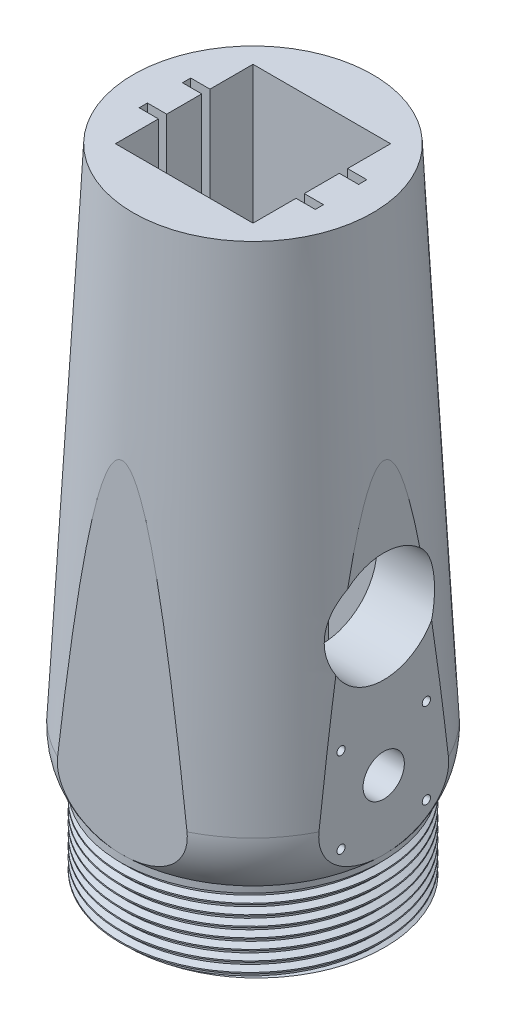
SolidWorks part; units mm, degrees
ref_plane "Front Plane" through (0, 0, 0) normal (0, 0, 1) x (1, 0, 0)
ref_plane "Top Plane" through (0, 0, 0) normal (0, 1, 0) x (1, 0, 0)
ref_plane "Right Plane" through (0, 0, 0) normal (1, 0, 0) x (0, 0, -1)
sketch "Sketch2" plane through (0, 0, 0) normal (0, 1, 0) x (1, 0, 0)
  circle A0 centre (0, 0) radius 47.5
  dimension "D1" = 95
extrude "Boss-Extrude1" add sketch "Sketch2" along normal blind 30
thread "Thread2" pitch 3.6286 method cut profile "Thread Profile2" start angle 0, offset 0, length 30, pitch 3.6286, diameter 95
ref_plane "Plane2" through (-47.5, 30, 0) normal (0, 0, 1) x (-1, 0, 0)
sketch "Thread Profile2" plane through (-47.5, 30, 0) normal (0, 0, 1) x (-1, 0, 0)
  line L0 (0, 0) -> (0, 3.6286) construction
  line L11 (0, 0) -> (0, 3.175)
  line L12 (0, 3.175) -> (-1.964, 2.0411)
  line L13 (-1.964, 2.0411) -> (-1.964, 1.1339)
  line L15 (-1.964, 1.1339) -> (0, 0)
  line L17 (-1.964, 1.5875) -> (0, 1.5875) construction
  point P2 (0, 0)
  dimension "Pitch" = 3.6286
  dimension "Profile_Angle" = 60
  dimension "Profile_Land" = 0.9071
  dimension "Profile_Height" = 1.964
sketch "Sketch12" plane through (0, 30, 0) normal (0, 1, 0) x (1, 0, 0)
  circle A0 centre (0, 0) radius 54
  dimension "D1" = 108
extrude "Boss-Extrude2" add sketch "Sketch12" along normal blind 200 draft 3
sketch "Sketch13" plane through (0, 230, 0) normal (0, 1, 0) x (1, 0, 0)
  line L1 (-25, 25) -> (25, 25)
  line L2 (-25, 25) -> (-25, -25)
  line L3 (-25, -25) -> (25, -25)
  line L4 (25, 25) -> (25, -25)
  line L5 (-25, 25) -> (25, -25) construction
  line L6 (-25, -25) -> (25, 25) construction
  point P0 (0, 0)
  dimension "D1" = 50
  dimension "D2" = 50
extrude "Cut-Extrude2" cut sketch "Sketch13" against normal up to surface (200 mm away) up to face at (0, 30, 54)
sketch "Sketch14" plane through (0, 230, 0) normal (0, 1, 0) x (1, 0, 0)
  line L5 (-47.5, 47.5) -> (47.5, 47.5)
  line L6 (-47.5, 47.5) -> (-47.5, -47.5)
  line L7 (-47.5, -47.5) -> (47.5, -47.5)
  line L8 (47.5, 47.5) -> (47.5, -47.5)
  line L9 (-47.5, 47.5) -> (47.5, -47.5) construction
  line L10 (-47.5, -47.5) -> (47.5, 47.5) construction
  circle A3 centre (0, 0) radius 67.1751
  point P0 (0, 0)
  point P1 (0, 0)
  dimension "D1" = 95
extrude "Cut-Extrude3" cut sketch "Sketch14" against normal up to surface (200 mm away) contours L6 A3 | L5 A3 | L8 A3 | L7 A3 region at (0, 230, -55.478) region at (-55.478, 230, 0) region at (55.478, 230, 0) region at (0, 230, 55.478) up to face at (0, 30, 54)
fillet "Fillet2" radius 30 4 edges at (-38.1838, 30, 38.1838) (-38.1838, 30, -38.1838) (38.1838, 30, 38.1838) (38.1838, 30, -38.1838)
sketch "Sketch15" plane through (-25, 0, 0) normal (1, 0, 0) x (0, 0, -1)
  line L1 (-21.15, 76.15) -> (21.15, 76.15)
  line L2 (-21.15, 76.15) -> (-21.15, 33.85)
  line L3 (-21.15, 33.85) -> (21.15, 33.85)
  line L4 (21.15, 76.15) -> (21.15, 33.85)
  line L5 (-21.15, 76.15) -> (21.15, 33.85) construction
  line L6 (-21.15, 33.85) -> (21.15, 76.15) construction
  point P0 (0, 55)
  dimension "D1" = 42.3
  dimension "D2" = 55
extrude "Cut-Extrude4" cut sketch "Sketch15" against normal up to next
sketch "Sketch16" plane through (0, 0, 25) normal (0, 0, -1) x (-1, 0, 0)
  line L1 (-2.5, 76) -> (2.5, 76)
  line L2 (-2.5, 76) -> (-2.5, 34)
  line L3 (-2.5, 34) -> (2.5, 34)
  line L4 (2.5, 76) -> (2.5, 34)
  line L5 (-2.5, 76) -> (2.5, 34) construction
  line L6 (-2.5, 34) -> (2.5, 76) construction
  point P0 (0, 55)
  dimension "D1" = 42
  dimension "D2" = 55
  dimension "D3" = 5
extrude "Boss-Extrude3" add sketch "Sketch16" along normal up to next
sketch "Sketch17" plane through (2.5, 0, 0) normal (1, 0, 0) x (0, 0, -1)
  line L1 (-15.5, 70.5) -> (15.5, 70.5)
  line L2 (-15.5, 70.5) -> (-15.5, 39.5)
  line L3 (-15.5, 39.5) -> (15.5, 39.5)
  line L4 (15.5, 70.5) -> (15.5, 39.5)
  line L5 (-15.5, 70.5) -> (15.5, 39.5) construction
  line L6 (-15.5, 39.5) -> (15.5, 70.5) construction
  circle A0 centre (-15.5, 70.5) radius 1.5
  circle A1 centre (15.5, 70.5) radius 1.5
  circle A2 centre (-15.5, 39.5) radius 1.5
  circle A3 centre (15.5, 39.5) radius 1.5
  circle A4 centre (0, 55) radius 7.5
  point P0 (0, 55)
  dimension "D3" = 3
  dimension "D4" = 15
  dimension "D1" = 31
  dimension "D2" = 31
  dimension "55" = 55
extrude "Cut-Extrude5" cut sketch "Sketch17" against normal through all both and the other way through all contours A0 | A4 | A1 | A2 | A3
sketch "Sketch18" plane through (0, 230, 0) normal (0, 1, 0) x (1, 0, 0)
  circle A0 centre (0, 0) radius 43.5184
  dimension "D1" = 87.0369
sketch "Sketch19" plane through (47.5, 0, 0) normal (1, 0, 0) x (0, 0, -1)
  circle A0 centre (0, 105) radius 20
  circle A1 centre (0, 55) radius 7.5 construction
  dimension "D1" = 40
  dimension "D2" = 50
extrude "Cut-Extrude6" cut sketch "Sketch19" against normal through all both and the other way through all
sketch "Sketch20" plane through (-25, 0, 0) normal (1, 0, 0) x (0, 0, -1)
  line L0 (25, 230) -> (-25, 230) construction
  line L1 (6.366, 105) -> (9.366, 105)
  line L2 (6.366, 105) -> (6.366, 230)
  line L3 (6.366, 230) -> (9.366, 230)
  line L4 (9.366, 105) -> (9.366, 230)
  line L6 (-6.366, 105) -> (-9.366, 105)
  line L7 (-6.366, 105) -> (-6.366, 230)
  line L8 (-6.366, 230) -> (-9.366, 230)
  line L9 (-9.366, 105) -> (-9.366, 230)
  circle A0 centre (0, 105) radius 6.366
  circle A1 centre (0, 105) radius 20 construction
  circle M3 centre (0, 105) radius 20
  line M10 (25, 230) -> (-25, 230)
  dimension "D1" = 12.732
  dimension "D2" = 3
  dimension "D3" = 3
extrude "Cut-Extrude7" cut sketch "Sketch20" against normal blind 7 and the other way blind 57 contours L9 L7 M3 M10 | L4 L2 M3 M10 region at (-25, 176.6814, -7.869) region at (-25, 176.6814, 7.869)
